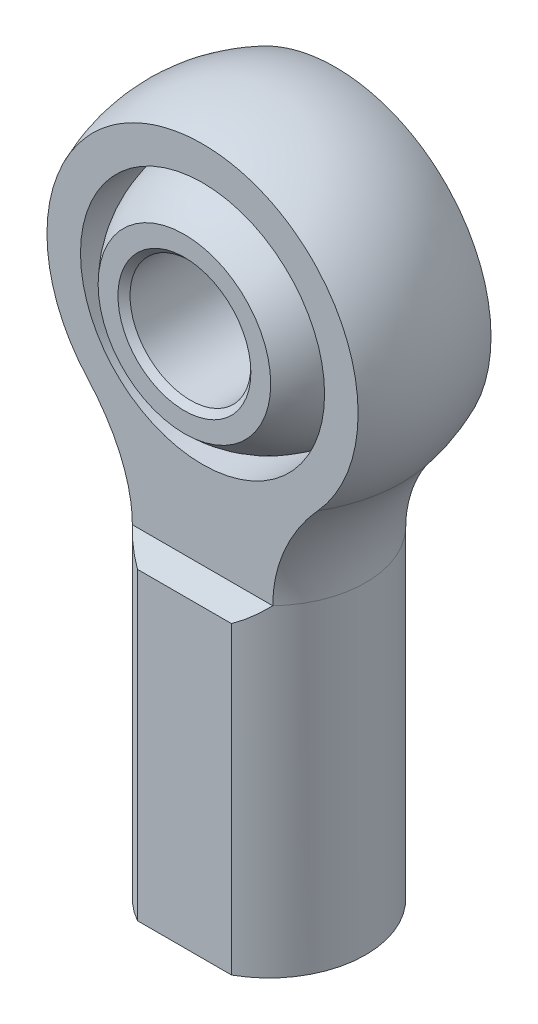
SolidWorks part; units mm, degrees
material "6061-T6 (SS)"
ref_plane "Front" through (0, 0, 0) normal (0, 0, 1) x (1, 0, 0)
ref_plane "Top" through (0, 0, 0) normal (0, 1, 0) x (1, 0, 0)
ref_plane "Right" through (0, 0, 0) normal (1, 0, 0) x (0, 0, -1)
sketch "Sketch1" plane through (0, 0, 0) normal (0, 0, 1) x (1, 0, 0)
  line L0 (0, 0) -> (0, -17.4625) construction
  line L1 (0, -17.4625) -> (3.9688, -17.4625) construction
  line L2 (3.9688, -17.4625) -> (3.9688, 0) construction
  line L3 (3.9688, 0) -> (0, 0) construction
  line L5 (0, 28.575) -> (0, 0) construction
  line L6 (0, 28.575) -> (11.1125, 28.575) construction
  line L7 (11.1125, 28.575) -> (11.1125, 17.4625) construction
  line L8 (-3.9687, -17.4625) -> (-3.9687, 0) construction
  line L9 (6.35, 3.7143) -> (6.35, -17.4625)
  line L10 (4.3177, 0) -> (5.5499, 0) construction
  line L11 (5.5499, 0) -> (5.5499, -17.4625) construction
  line L12 (6.35, -17.4625) -> (0, -17.4625)
  line L13 (0, -17.4625) -> (0, 3.7143)
  line L14 (0, 3.7143) -> (6.35, 3.7143)
  line L15 (0, 6.35) -> (6.6671, 6.35) construction
  arc A0 (8.7313, 10.5884) -> (0, 28.575) centre (0, 17.4625) ccw construction
  circle A1 centre (0, 17.4625) radius 3.9688 construction
  circle A2 centre (0, 17.4625) radius 7.9375 construction
  circle A3 centre (0, 17.4625) radius 8.0169 construction
  arc A4 (8.7313, 10.5884) -> (0, 6.35) centre (0, 17.4625) cw construction
  arc A5 (8.7313, 10.5884) -> (6.35, 3.7143) centre (17.4625, 3.7143) ccw construction
  dimension "A" = 7.9375
  dimension "Ball Dia" = 15.875
  dimension "B" = 22.225
  dimension "D1" = 16.0337
  dimension "D" = 34.925
  dimension "E" = 17.4625
  dimension "Thread Dia" = 7.9375
  dimension "Body Dia" = 12.7
  dimension "Wrench Flats" = 11.0998
revolve "Revolve1" add sketch "Sketch1" angle 360 about L5
sketch "Sketch12" plane through (0, 0, 0) normal (0, 0, 1) x (1, 0, 0)
  line L1 (0, 0) -> (0, 3.7143) construction
  line L2 (6.35, -17.4625) -> (0, -17.4625) construction
  line L3 (3.9688, -17.4625) -> (3.9688, 0) construction
  line L4 (3.9688, 0) -> (0, 0) construction
  line L5 (3.9688, -17.4625) -> (0, -17.4625)
  line L6 (3.9688, -17.4625) -> (3.9688, 0)
  line L7 (3.9688, 0) -> (0, 0)
  line L8 (0, -17.4625) -> (0, 3.7143) construction
  line L9 (0, -17.4625) -> (0, 0)
revolve "Revolve4" add sketch "Sketch12" angle 360 about L1
sketch "Sketch15" plane through (0, 0, 0) normal (0, 1, 0) x (1, 0, 0)
  circle A0 centre (0, 0) radius 3.9688 construction
  circle A1 centre (0, 0) radius 3.9688
curve "Helix/Spiral1" pitch 1.0583 height 18.5208 turns 17.5 parameters "pitch"=1.0583
sketch "Sketch16" plane through (0, 0, 0) normal (0, 0, 1) x (1, 0, 0)
  line L0 (-3.9688, 0.926) -> (-3.9688, 0)
  line L1 (-3.9688, 0) -> (-3.2813, 0.3969)
  line L2 (-3.2813, 0.3969) -> (-3.2813, 0.5292)
  line L3 (-3.2813, 0.5292) -> (-3.9688, 0.926)
  line L4 (-3.2813, 0.463) -> (-3.9688, 0.463) construction
  line L5 (-3.625, 0.1984) -> (-3.625, 0.7276) construction
  line L6 (3.9688, 0) -> (-3.9688, 0) construction
  dimension "D1" = 60
  dimension "D2" = 0.1323
  dimension "D3" = 0.5292
sweep "Cut-Sweep1" cut profiles "Sketch16" path "Helix/Spiral1" align with end faces yes
sketch "Sketch14" plane through (0, -17.4625, 0) normal (0, 1, 0) x (-1, 0, 0)
  line L0 (-5.5499, 0) -> (5.5499, 0) construction
  line L1 (5.5499, 5.5499) -> (-5.5499, 5.5499)
  line L2 (5.5499, 5.5499) -> (5.5499, -5.5499) construction
  line L3 (5.5499, -5.5499) -> (-5.5499, -5.5499)
  line L4 (-5.5499, 5.5499) -> (-5.5499, -5.5499) construction
  line L5 (-5.5499, -5.5499) -> (-5.5499, -6.35)
  line L6 (-5.5499, -6.35) -> (5.5499, -6.35)
  line L7 (5.5499, -6.35) -> (5.5499, -5.5499)
  line L8 (5.5499, 5.5499) -> (5.5499, 6.35)
  line L9 (5.5499, 6.35) -> (-5.5499, 6.35)
  line L10 (-5.5499, 6.35) -> (-5.5499, 5.5499)
  circle A0 centre (0, 0) radius 6.35 construction
extrude "Cut-Extrude5" cut sketch "Sketch14" along normal through all
combine bodies "Combine1" operation type subtract main body 123 bodies to subtract 127
sketch "Sketch17" plane through (0, -17.4625, 0) normal (0, -1, 0) x (1, 0, 0)
  circle A2 centre (0, 0) radius 4.0196
  circle A3 centre (0, 0) radius 4.0196
  dimension "D1" = 0.0508
extrude "Extrude1" cut sketch "Sketch17" against normal through all draft 45
sketch "Sketch4" plane through (0, 0, 0) normal (0, 0, 1) x (1, 0, 0)
  line L3 (6.35, 3.7143) -> (0, 3.7143)
  line L4 (0, 28.575) -> (0, 0) construction
  line L5 (0, 28.575) -> (0, 3.7143)
  line L6 (0, 28.575) -> (0, 31.115) construction
  arc A0 (8.7313, 10.5884) -> (0, 28.575) centre (0, 17.4625) ccw construction
  arc A1 (8.7313, 10.5884) -> (0, 28.575) centre (0, 17.4625) ccw
  arc A2 (8.7313, 10.5884) -> (6.35, 3.7143) centre (17.4625, 3.7143) ccw construction
  arc A3 (8.7313, 10.5884) -> (6.35, 3.7143) centre (17.4625, 3.7143) ccw
  dimension "D1" = 2.54
revolve "Revolve2" add sketch "Sketch4" angle 360 about L6
sketch "Sketch5" plane through (0, 0, 0) normal (1, 0, 0) x (0, 0, -1)
  line L0 (4.3656, 28.575) -> (11.1125, 28.575)
  line L1 (-4.3656, 28.575) -> (4.3656, 28.575) construction
  line L2 (-4.3656, 28.575) -> (-4.3656, 3.7143)
  line L3 (-4.3656, 3.7143) -> (4.3656, 3.7143) construction
  line L4 (4.3656, 28.575) -> (4.3656, 3.7143)
  line L5 (11.1125, 28.575) -> (11.1125, 3.7143)
  line L6 (11.1125, 3.7143) -> (4.3656, 3.7143) construction
  line L7 (-4.3656, 3.7143) -> (-11.1125, 3.7143) construction
  line L8 (-11.1125, 3.7143) -> (-11.1125, 28.575)
  line L9 (-11.1125, 28.575) -> (-4.3656, 28.575)
  line L10 (-4.3656, 3.7143) -> (-5.5499, 2.5301)
  line L11 (-19.05, -53.975) -> (-19.05, 8.47) construction
  line L12 (-5.5499, 2.5301) -> (-11.1125, 2.5301)
  line L13 (-11.1125, 3.7143) -> (-11.1125, 2.5301)
  line L14 (4.3656, 3.7143) -> (5.5499, 2.5301)
  line L15 (5.5499, 2.5301) -> (11.1125, 2.5301)
  line L16 (11.1125, 2.5301) -> (11.1125, 3.7143)
  line L17 (-5.5499, -17.4625) -> (-5.5499, 3.7143) construction
  line L18 (5.5499, 3.7143) -> (5.5499, -17.4625) construction
  arc A0 (8.7312, 10.5884) -> (-8.7312, 10.5884) centre (0, 17.4625) ccw construction
  dimension "D1" = 14.6844
  dimension "F" = 8.7312
extrude "Cut-Extrude1" cut sketch "Sketch5" against normal through all and the other way through all
sketch "Sketch6" plane through (0, 0, 0) normal (0, 0, 1) x (1, 0, 0)
  circle A0 centre (0, 17.4625) radius 8.0169 construction
  circle A1 centre (0, 17.4625) radius 8.0169
extrude "Cut-Extrude2" cut sketch "Sketch6" against normal through all and the other way through all
sketch "Sketch7" plane through (0, 0, 0) normal (0, 0, 1) x (1, 0, 0)
  line L0 (0, 25.4) -> (0, 9.525)
  line L1 (0, 28.575) -> (0, 0) construction
  line L2 (0, 0) -> (0, 9.525) construction
  arc A0 (0, 9.525) -> (0, 25.4) centre (0, 17.4625) ccw
  circle A1 centre (0, 17.4625) radius 7.9375 construction
revolve "Revolve3" add sketch "Sketch7" angle 360 about L2
sketch "Sketch8" plane through (0, 0, 0) normal (1, 0, 0) x (0, 0, -1)
  line L0 (-4.3656, 28.575) -> (4.3656, 28.575) construction
  line L1 (-5.5562, 28.575) -> (5.5562, 28.575) construction
  line L2 (-5.5562, 28.575) -> (-5.5563, 3.7143)
  line L3 (-5.5563, 3.7143) -> (5.5563, 3.7143) construction
  line L4 (5.5562, 28.575) -> (5.5563, 3.7143)
  line L5 (5.5562, 28.575) -> (11.1125, 28.575)
  line L6 (11.1125, 28.575) -> (11.1125, 3.7143)
  line L7 (11.1125, 3.7143) -> (5.5563, 3.7143)
  line L8 (-5.5563, 3.7143) -> (-11.1125, 3.7143)
  line L9 (-11.1125, 3.7143) -> (-11.1125, 28.575)
  line L10 (-11.1125, 28.575) -> (-5.5562, 28.575)
  dimension "C" = 11.1125
extrude "Cut-Extrude3" cut sketch "Sketch8" against normal through all and the other way through all
sketch "Sketch10" plane through (0, 0, 0) normal (0, 0, 1) x (1, 0, 0)
  circle A0 centre (0, 17.4625) radius 3.9688 construction
  circle A1 centre (0, 17.4625) radius 3.9688
extrude "Cut-Extrude4" cut sketch "Sketch10" against normal through all and the other way through all
chamfer "Chamfer1" distance 0.3969 angle 45 2 edges at (3.9688, 17.4625, -5.5563) (3.9688, 17.4625, 5.5562)
sketch "Sketch11" plane through (0, 0, 0) normal (1, 0, 0) x (0, 0, -1)
  line L0 (0, 17.4625) -> (-5.5562, 18.1447) construction
  line L1 (4.3656, 17.4625) -> (-4.3656, 17.4625) construction
  line L2 (0, 17.4625) -> (-5.5562, 16.7803) construction
  line L3 (0, 28.575) -> (0, 0) construction
  line L4 (-5.5562, 28.575) -> (-5.5562, 3.7143) construction
  line L5 (0, 17.4625) -> (0.0074, 17.4625) construction
  dimension "Swivel" = 14
sketch "Sketch18" plane through (0, 0, 0) normal (0, 0, 1) x (1, 0, 0)
sketch "Sketch19" plane through (0, 0, 0) normal (0, 0, 1) x (1, 0, 0)
  line L1 (-3.9688, 0) -> (3.9688, 0)
  line L2 (-3.9688, 0) -> (-3.9688, -17.4625)
  line L3 (-3.9688, -17.4625) -> (3.9688, -17.4625)
  line L4 (3.9688, 0) -> (3.9688, -17.4625)
equation "\"D1@Sketch1\"=\"Ball Dia@Sketch1\"*1.01"
equation "\"D1@Chamfer1\"=\"A@Sketch1\"/20"
equation "\"D2@Sketch16\" = \"pitch@Helix/Spiral1\"*.125"
equation "\"D3@Sketch16\" = \"pitch@Helix/Spiral1\"*.50"
equation "\"D3@Helix/Spiral1\" = \"E@Sketch1\"+\"pitch@Helix/Spiral1\""
